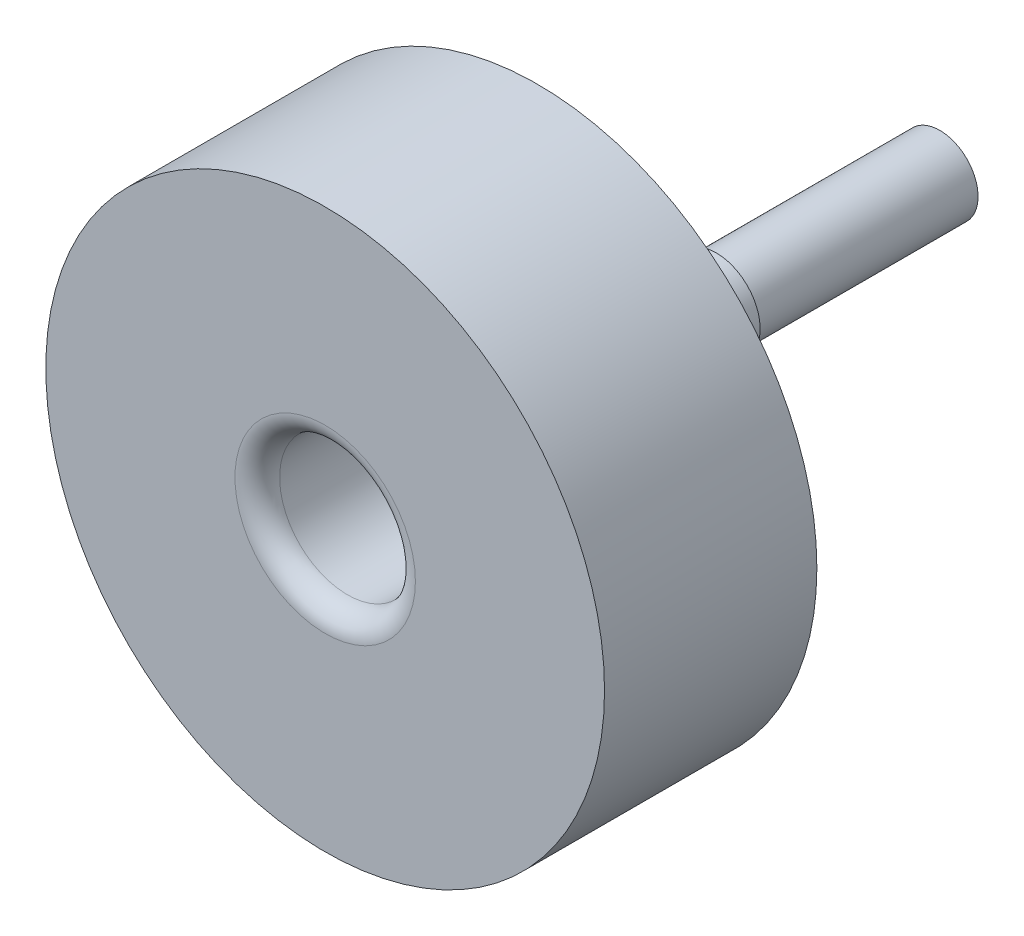
SolidWorks part; units mm, degrees
ref_plane "Ebene vorne" through (0, 0, 0) normal (0, 0, 1) x (1, 0, 0)
ref_plane "Ebene oben" through (0, 0, 0) normal (0, 1, 0) x (1, 0, 0)
ref_plane "Ebene rechts" through (0, 0, 0) normal (1, 0, 0) x (0, 0, -1)
sketch "Skizze1" plane through (0, 0, 0) normal (0, 0, 1) x (1, 0, 0)
  circle A0 centre (0, 0) radius 6
  dimension "D1" = 12
extrude "Aufsatz-Linear austragen1" add sketch "Skizze1" along normal blind 9
sketch "Skizze2" plane through (0, 0, 0) normal (0, 0, -1) x (-1, 0, 0)
  circle A0 centre (0, 0) radius 3.925
  dimension "D1" = 7.85
extrude "Aufsatz-Linear austragen2" add sketch "Skizze2" along normal blind 7
sketch "Skizze3" plane through (0, 0, 9) normal (0, 0, 1) x (1, 0, 0)
  circle A0 centre (0, 0) radius 25
  dimension "D1" = 50
extrude "Aufsatz-Linear austragen3" add sketch "Skizze3" along normal blind 19
sketch "Skizze4" plane through (0, 0, 28) normal (0, 0, 1) x (1, 0, 0)
  circle A0 centre (0, 0) radius 6.075
  dimension "D1" = 12.15
extrude "Schnitt-Linear austragen2" cut sketch "Skizze4" against normal blind 10
fillet "Verrundung1" radius 2 1 edges at (6.075, 0, 28)
sketch "Skizze5" plane through (0, 0, -7) normal (0, 0, -1) x (-1, 0, 0)
  circle A0 centre (0, 0) radius 3.425
  dimension "D1" = 6.85
extrude "Aufsatz-Linear austragen4" add sketch "Skizze5" along normal blind 20
